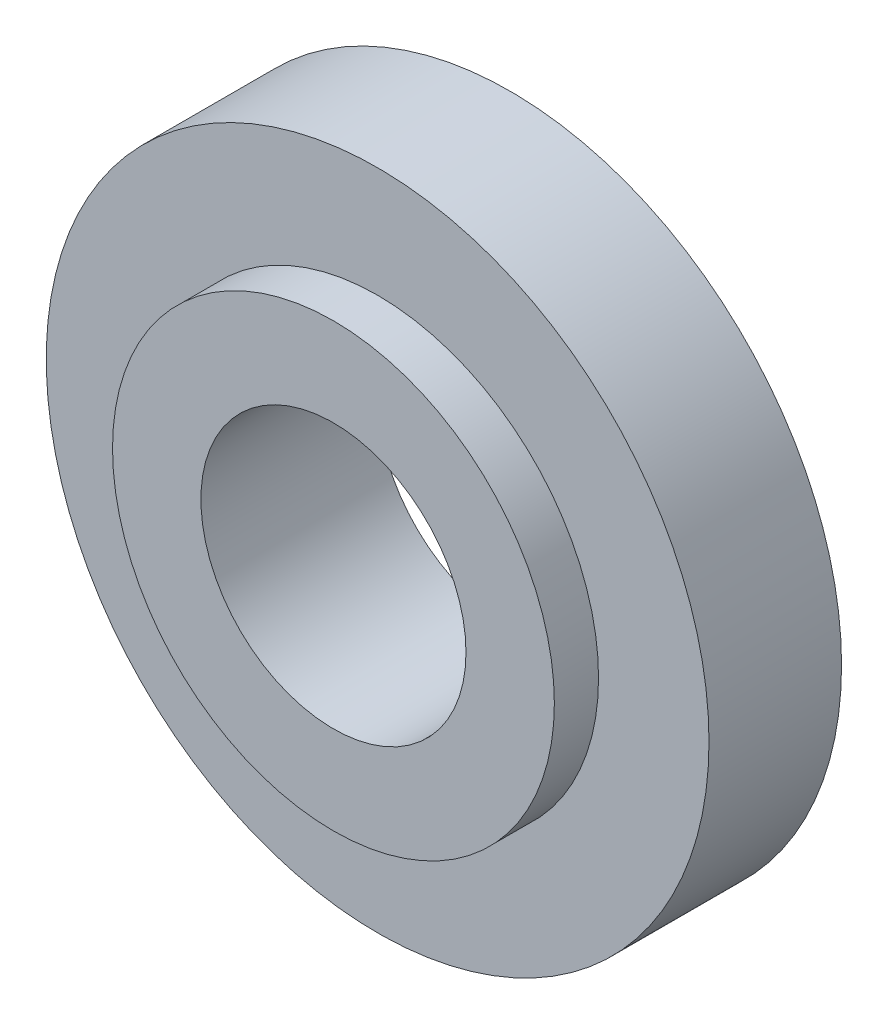
SolidWorks part; units mm, degrees
ref_plane "Front Plane" through (0, 0, 0) normal (0, 0, 1) x (1, 0, 0)
ref_plane "Top Plane" through (0, 0, 0) normal (0, 1, 0) x (1, 0, 0)
ref_plane "Right Plane" through (0, 0, 0) normal (1, 0, 0) x (0, 0, -1)
sketch "Sketch1" plane through (0, 0, 0) normal (0, 0, 1) x (1, 0, 0)
  circle A0 centre (0, 0) radius 1.5
  circle A1 centre (0, 0) radius 2.5
  circle A2 centre (0, 0) radius 3.75
  dimension "D1" = 7.5
  dimension "D2" = 5
  dimension "D3" = 3
extrude "Boss-Extrude2" add sketch "Sketch1" against normal blind 1.5 contours A2 A1 | A1 A0 region at (-2.4293, 0, 0) region at (-3.6439, 0, 0)
extrude "Boss-Extrude3" add sketch "Sketch1<4>" along normal blind 0.5 contours A1 A0 region at (-2.4293, 0, 0)
sketch "Sketch1<4>" plane through (0, 0, 0) normal (0, 0, 1) x (1, 0, 0) same geometry as "Sketch1"
